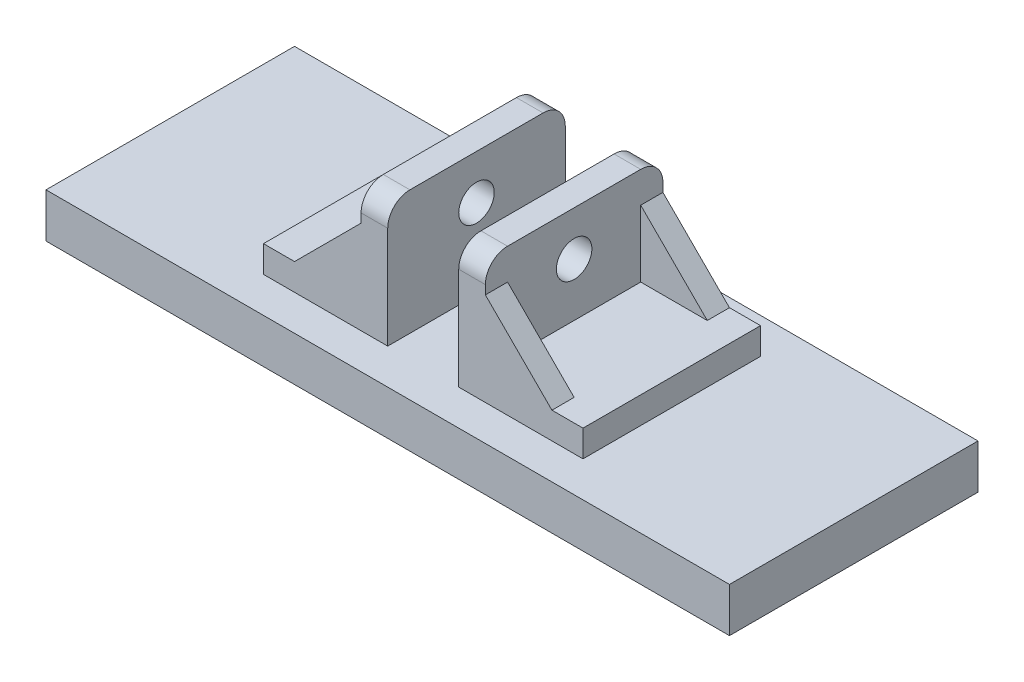
SolidWorks part; units mm, degrees
ref_plane "Front Plane" through (0, 0, 0) normal (0, 0, 1) x (1, 0, 0)
ref_plane "Top Plane" through (0, 0, 0) normal (0, 1, 0) x (1, 0, 0)
ref_plane "Right Plane" through (0, 0, 0) normal (1, 0, 0) x (0, 0, -1)
sketch "Sketch1" plane through (0, 0, 0) normal (0, 1, 0) x (1, 0, 0)
  line L1 (77, 28) -> (-77, 28)
  line L2 (77, 28) -> (77, -28)
  line L3 (77, -28) -> (-77, -28)
  line L4 (-77, 28) -> (-77, -28)
  line L5 (77, 28) -> (-77, -28) construction
  line L6 (77, -28) -> (-77, 28) construction
  point P0 (0, 0)
  dimension "D1" = 154
  dimension "D2" = 56
extrude "plate" add sketch "Sketch1" along normal blind 10
sketch "Sketch2" plane through (0, 0, 0) normal (0, 0, 1) x (1, 0, 0)
  line L0 (-8, 10) -> (-8, 38)
  line L1 (-77, 10) -> (77, 10) construction
  line L2 (-8, 38) -> (-14, 38)
  line L3 (-14, 38) -> (-14, 16)
  line L4 (-14, 16) -> (-36, 16)
  line L5 (-36, 16) -> (-36, 10)
  line L6 (-36, 10) -> (-8, 10)
  line L7 (-14, 31) -> (-29, 16)
  line L8 (0, 0) -> (0, 10) construction
  line L9 (14, 31) -> (29, 16)
  line L10 (36, 16) -> (36, 10)
  line L11 (14, 16) -> (36, 16)
  line L12 (14, 38) -> (14, 16)
  line L13 (8, 38) -> (14, 38)
  line L14 (8, 10) -> (8, 38)
  line L15 (36, 10) -> (8, 10)
  dimension "D1" = 45
  dimension "D2" = 6
  dimension "D3" = 8
  dimension "D4" = 28
  dimension "D5" = 15
extrude "Boss-Extrude1" add sketch "Sketch2" along normal mid plane 40 contours L0 L2 L3 L4 L5 L6 | L10 L15 L14 L13 L12 L11
extrude "Corner" add sketch "Sketch2<4>" against normal blind 5 from offset 15 contours L3 L7 L4 | L9 L12 L11 region at (-19, 21, 0) region at (19, 21, 0) offset against normal yes
sketch "Sketch2<4>" plane through (0, 0, 0) normal (0, 0, 1) x (1, 0, 0) same geometry as "Sketch2"
extrude "Corner2" add sketch "Sketch2<3>" along normal blind 5 from offset 15 contours L3 L7 L4 | L9 L12 L11 region at (-19, 21, 0) region at (19, 21, 0)
sketch "Sketch2<3>" plane through (0, 0, 0) normal (0, 0, 1) x (1, 0, 0) same geometry as "Sketch2"
sketch "Sketch3" plane through (-14, 0, 0) normal (-1, 0, 0) x (0, 0, 1)
  line L0 (20, 38) -> (-20, 38) construction
  circle A0 centre (0, 28) radius 4
  dimension "D2" = 8
  dimension "D1" = 10
extrude "Cut-Extrude1" cut sketch "Sketch3" against normal up to surface (28 mm away) up to face at (14, 29, 0)
fillet "Fillet1" radius 5 4 edges at (-11, 38, -20) (11, 38, 20) (11, 38, -20) (-11, 38, 20)
equation "\"D1@Sketch1\"=144 + 10"
equation "\"D2@Sketch1\"=46+10"
